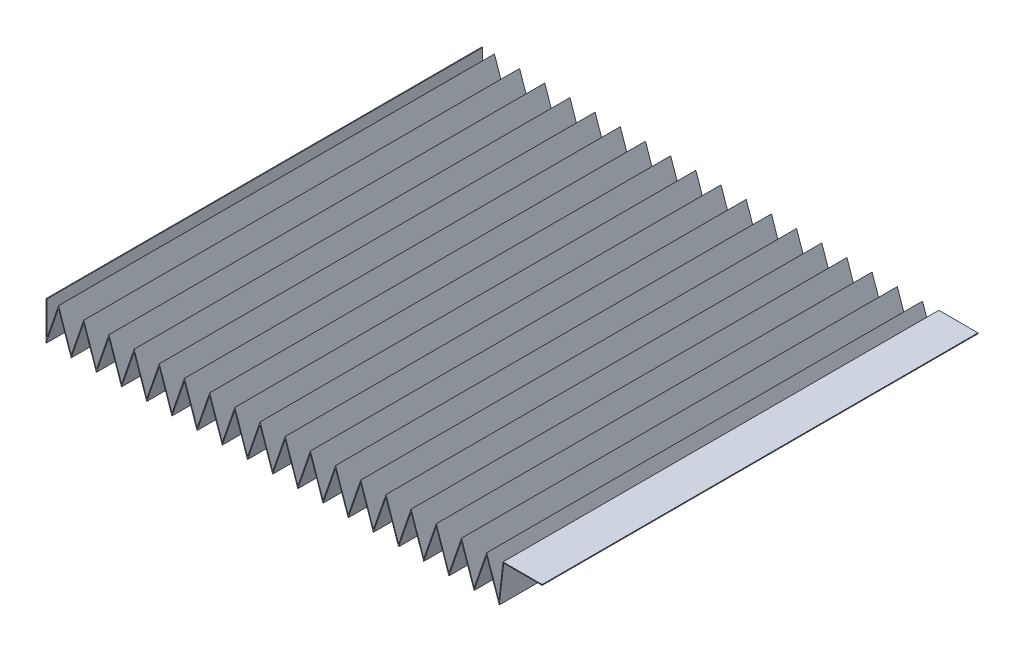
SolidWorks part; units mm, degrees
ref_plane "Front Plane" through (0, 0, 0) normal (0, 0, 1) x (1, 0, 0)
ref_plane "Top Plane" through (0, 0, 0) normal (0, 1, 0) x (1, 0, 0)
ref_plane "Right Plane" through (0, 0, 0) normal (1, 0, 0) x (0, 0, -1)
sketch "Sketch1" plane through (0, 0, 0) normal (0, 0, 1) x (1, 0, 0)
  line L0 (0, 0) -> (4.9112, 14.279)
  line L1 (4.9112, 14.279) -> (9.8223, 0)
  line L2 (0, 0) -> (511, 0) construction
  line L3 (9.8223, 0) -> (14.7335, 14.279)
  line L4 (14.7335, 14.279) -> (19.6447, 0)
  line L5 (19.6447, 0) -> (24.5558, 14.279)
  line L6 (24.5558, 14.279) -> (29.467, 0)
  line L7 (29.467, 0) -> (34.3782, 14.279)
  line L8 (34.3782, 14.279) -> (39.2893, 0)
  line L9 (39.2893, 0) -> (44.2005, 14.279)
  line L10 (44.2005, 14.279) -> (49.1117, 0)
  line L11 (49.1117, 0) -> (54.0228, 14.279)
  line L12 (54.0228, 14.279) -> (58.934, 0)
  line L13 (58.934, 0) -> (63.8451, 14.279)
  line L14 (63.8451, 14.279) -> (68.7563, 0)
  line L15 (68.7563, 0) -> (73.6675, 14.279)
  line L16 (73.6675, 14.279) -> (78.5786, 0)
  line L17 (78.5786, 0) -> (83.4898, 14.279)
  line L18 (83.4898, 14.279) -> (88.401, 0)
  line L19 (0, 0) -> (0, 15.1)
  line L20 (88.401, 0) -> (93.3121, 14.279)
  line L21 (93.3121, 14.279) -> (98.2233, 0)
  line L22 (98.2233, 0) -> (103.1345, 14.279)
  line L23 (103.1345, 14.279) -> (108.0456, 0)
  line L24 (108.0456, 0) -> (112.9568, 14.279)
  line L25 (112.9568, 14.279) -> (117.868, 0)
  line L26 (117.868, 0) -> (122.7791, 14.279)
  line L27 (122.7791, 14.279) -> (127.6903, 0)
  line L28 (127.6903, 0) -> (132.6015, 14.279)
  line L29 (132.6015, 14.279) -> (137.5126, 0)
  line L30 (137.5126, 0) -> (142.4238, 14.279)
  line L31 (142.4238, 14.279) -> (147.335, 0)
  line L32 (147.335, 0) -> (152.2461, 14.279)
  line L33 (152.2461, 14.279) -> (157.1573, 0)
  line L34 (157.1573, 0) -> (162.0685, 14.279)
  line L35 (162.0685, 14.279) -> (166.9796, 0)
  line L36 (166.9796, 0) -> (171.8908, 14.279)
  line L37 (171.8908, 14.279) -> (176.8019, 0)
  line L38 (176.8019, 0) -> (178.5369, 15)
  line L39 (178.5369, 15) -> (193.5369, 15)
  line L41 (191.5369, 13.6) -> (191.5369, 34.6) construction
  dimension "D1" = 511
  dimension "D2" = 15.1
  dimension "D3" = 15
  dimension "D4" = 9.8223
  dimension "D6" = 15
  dimension "D7" = 2
  dimension "D5" = 18
extrude "Extrude-Thin1" add sketch "Sketch1" along normal mid plane 170 thin thin type one direction reverse wall 0.3
